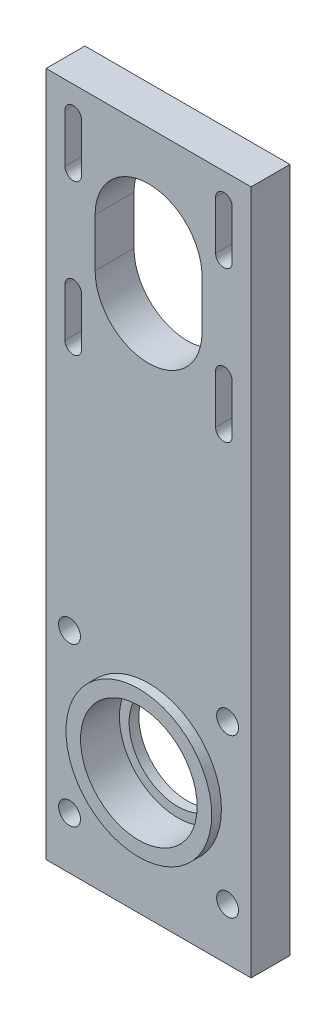
SolidWorks part; units mm, degrees
material "6061-T6 (SS)"
ref_plane "前基準面" through (0, 0, 0) normal (0, 0, 1) x (1, 0, 0)
ref_plane "上基準面" through (0, 0, 0) normal (0, 1, 0) x (1, 0, 0)
ref_plane "右基準面" through (0, 0, 0) normal (1, 0, 0) x (0, 0, -1)
sketch "草圖1" plane through (0, 0, 0) normal (0, 0, 1) x (1, 0, 0)
  line L1 (-21.1, -30) -> (21.1, -30)
  line L2 (-21.1, -30) -> (-21.1, 30)
  line L3 (-21.1, 30) -> (21.1, 30)
  line L4 (21.1, -30) -> (21.1, 30)
  line L5 (-21.1, -30) -> (21.1, 30) construction
  line L6 (-21.1, 30) -> (21.1, -30) construction
  point P0 (0, 0)
  dimension "D1" = 42.2
  dimension "D2" = 60
extrude "填料-伸長1" add sketch "草圖1" along normal mid plane 8
sketch "草圖5" plane through (0, 0, 4) normal (0, 0, 1) x (1, 0, 0)
  circle A0 centre (0, -3) radius 15
  point P3 (0, 0)
  point P5 (0, 0)
  dimension "D1" = 30
  dimension "D2" = 3
extrude "填料-伸長3" add sketch "草圖5" along normal blind 2
sketch "草圖6" plane through (0, 0, 6) normal (0, 0, 1) x (1, 0, 0)
  circle A0 centre (0, -3) radius 10
  point P3 (0, 0)
  point P4 (0, 0)
  point P5 (0, 0)
  point P7 (0, -2.5259)
  dimension "D1" = 20
  dimension "D2" = 3
extrude "除料-伸長3" cut sketch "草圖6" against normal through all
sketch "草圖7" plane through (0, 0, 6) normal (0, 0, 1) x (1, 0, 0)
  circle A0 centre (0, -3) radius 12
  point P3 (0, 0)
  point P4 (1.0122, -3.5157)
  dimension "D1" = 24
  dimension "D2" = 3
extrude "除料-伸長4" cut sketch "草圖7" against normal blind 8
sketch "草圖8" plane through (0, 30, 0) normal (0, 1, 0) x (1, 0, 0)
  line L1 (-21.1, 4) -> (21.1, 4)
  line L2 (-21.1, 4) -> (-21.1, -4)
  line L3 (-21.1, -4) -> (21.1, -4)
  line L4 (21.1, 4) -> (21.1, -4)
extrude "填料-伸長4" add sketch "草圖8" along normal blind 81
sketch "草圖9" plane through (0, 0, -4) normal (0, 0, -1) x (-1, 0, 0)
  line L0 (0, 111) -> (0, 90) construction
  line L1 (-21.1, 111) -> (21.1, 111) construction
  line L2 (0, 90) -> (0, 80) construction
  line L3 (11, 90) -> (11, 80)
  line L4 (-11, 90) -> (-11, 80)
  arc A1 (11, 90) -> (-11, 90) centre (0, 90) ccw
  arc A2 (-11, 80) -> (11, 80) centre (0, 80) ccw
  point P5 (0, 85)
  dimension "D1" = 22
  dimension "D2" = 21
  dimension "D3" = 10
extrude "除料-伸長5" cut sketch "草圖9" against normal through all
hole_wizard "M3 凹頭蓋螺釘的柱孔7" positions "草圖10" profile "草圖11" size "M3" standard "Ansi Metric" slot yes end condition through all
sketch "草圖10" plane through (0, 0, -4) normal (0, 0, 1) x (1, 0, 0)
  line L3 (15.5, 100.5) -> (-15.5, 100.5) construction
  line L4 (15.5, 100.5) -> (15.5, 69.5) construction
  line L5 (15.5, 69.5) -> (-15.5, 69.5) construction
  line L6 (-15.5, 100.5) -> (-15.5, 69.5) construction
  line L7 (15.5, 100.5) -> (-15.5, 69.5) construction
  line L8 (15.5, 69.5) -> (-15.5, 100.5) construction
  line L9 (0, 90) -> (0, 85) construction
  line L11 (15.5, 93.8) -> (15.5, 107.2) construction
  point P117 (15.5, 100.5)
  point P121 (15.5, 69.5)
  point P123 (-15.5, 100.5)
  point P125 (-15.5, 69.5)
  dimension "D1" = 13.4
  dimension "D2" = 31
  dimension "D3" = 5
sketch "草圖11" plane through (15.5, 100.5, -4) normal (1, 0, 0) x (0, 1, 0)
  line L0 (0, 0) -> (0, 10)
  line L1 (0, 10) -> (1.7, 10)
  line L3 (1.7, 10) -> (1.7, 3)
  line L4 (1.7, 3) -> (3.25, 3)
  line L5 (3.25, 3) -> (3.25, 0)
  line L7 (3.25, 0) -> (0, 0)
  line L11 (0, -6.35) -> (0, 107.95) construction
  dimension "貫穿孔直徑" = 3.4
  dimension "貫穿孔深度" = 10
  dimension "柱孔直徑" = 6.5
  dimension "柱孔深度" = 3
hole_wizard "M4 凹頭蓋螺釘的柱孔1" positions "草圖16" profile "草圖17" counterbore size "M4" standard "Ansi Metric" end condition through all
sketch "草圖16" plane through (0, 0, -4) normal (0, 0, -1) x (-1, 0, 0)
  line L1 (-16.2635, -19.2635) -> (16.2635, -19.2635) construction
  line L2 (-16.2635, -19.2635) -> (-16.2635, 13.2635) construction
  line L3 (-16.2635, 13.2635) -> (16.2635, 13.2635) construction
  line L4 (16.2635, -19.2635) -> (16.2635, 13.2635) construction
  line L5 (-16.2635, -19.2635) -> (16.2635, 13.2635) construction
  line L6 (-16.2635, 13.2635) -> (16.2635, -19.2635) construction
  point P1 (16.2635, 13.2635)
  point P122 (-16.2635, -19.2635)
  point P123 (-16.2635, 13.2635)
  point P124 (16.2635, -19.2635)
  point P137 (0, -3)
  dimension "D1" = 46
  dimension "D2" = 3
sketch "草圖17" plane through (-16.2635, 13.2635, -4) normal (1, 0, 0) x (0, 1, 0)
  line L0 (0, 0) -> (0, 10)
  line L1 (0, 10) -> (2.25, 10)
  line L3 (2.25, 10) -> (2.25, 4)
  line L4 (2.25, 4) -> (4, 4)
  line L5 (4, 4) -> (4, 0)
  line L7 (4, 0) -> (0, 0)
  line L11 (0, -6.35) -> (0, 107.95) construction
  dimension "貫穿孔直徑" = 4.5
  dimension "貫穿孔深度" = 10
  dimension "柱孔直徑" = 8
  dimension "柱孔深度" = 4
hole_wizard "M4x0.7 螺紋孔1" positions "草圖14" profile "草圖15" tap size "M4x0.7" standard "Ansi Metric"
sketch "草圖14" plane through (0, -30, 0) normal (0, -1, 0) x (-1, 0, 0)
  line L0 (10, 0) -> (-10, 0) construction
  point P0 (10, 0)
  point P1 (-10, 0)
  point P7 (0, 0)
  dimension "D1" = 20
sketch "草圖15" plane through (-10, -30, 0) normal (1, 0, 0) x (0, 0, -1)
  line L0 (0, 0) -> (0, 11.0914)
  line L1 (0, 11.0914) -> (1.65, 10.1)
  line L2 (1.65, 10.1) -> (1.65, 0)
  line L5 (1.65, 0) -> (0, 0)
  line L10 (0, 11.0914) -> (-1.65, 10.1) construction
  line L11 (0, -6.35) -> (0, 107.95) construction
  dimension "螺孔鑽直徑" = 3.3
  dimension "螺孔鑽深度" = 10.1
  dimension "導頭角度" = 118
